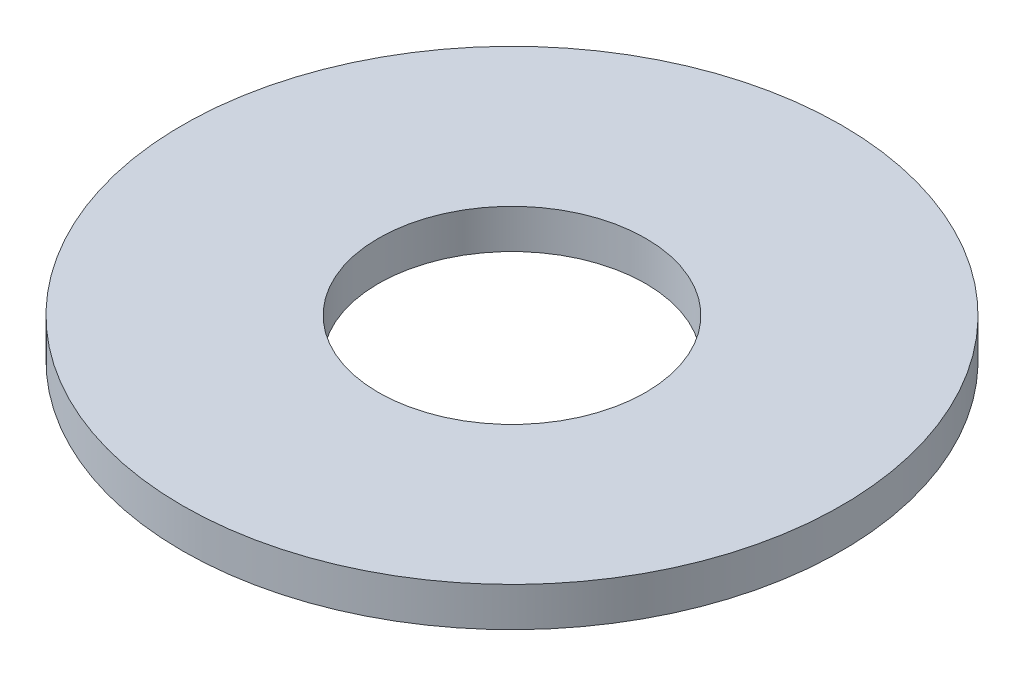
SolidWorks part; units mm, degrees
ref_plane "Front Plane" through (0, 0, 0) normal (0, 0, 1) x (1, 0, 0)
ref_plane "Top Plane" through (0, 0, 0) normal (0, 1, 0) x (1, 0, 0)
ref_plane "Right Plane" through (0, 0, 0) normal (1, 0, 0) x (0, 0, -1)
sketch "Sketch1" plane through (0, 0, 0) normal (0, 1, 0) x (1, 0, 0)
  circle A0 centre (0, 0) radius 92.5
  dimension "FLANGE_OD" = 185
extrude "Boss-Extrude1" add sketch "Sketch1" along normal blind 11
sketch "Sketch2" plane through (0, 0, 0) normal (0, 1, 0) x (1, 0, 0)
  circle A0 centre (0, 0) radius 37.5
  dimension "BORE_D" = 75
extrude "Cut-Extrude1" cut sketch "Sketch2" along normal through all
sketch "Sketch3" plane through (0, 11, 0) normal (0, 1, 0) x (1, 0, 0)
  circle A0 centre (0, 0) radius 28.6219 construction
  circle A1 centre (-28.6219, 0) radius 5.7566
  dimension "BOLT_D" = 11.5133
  dimension "BOLT_PCD" = 57.2439
extrude "Cut-Extrude2" cut sketch "Sketch3" against normal blind 9.353 rebuild error yes
pattern_circular "CirPattern1" count 6 over 360 rebuild error yes
